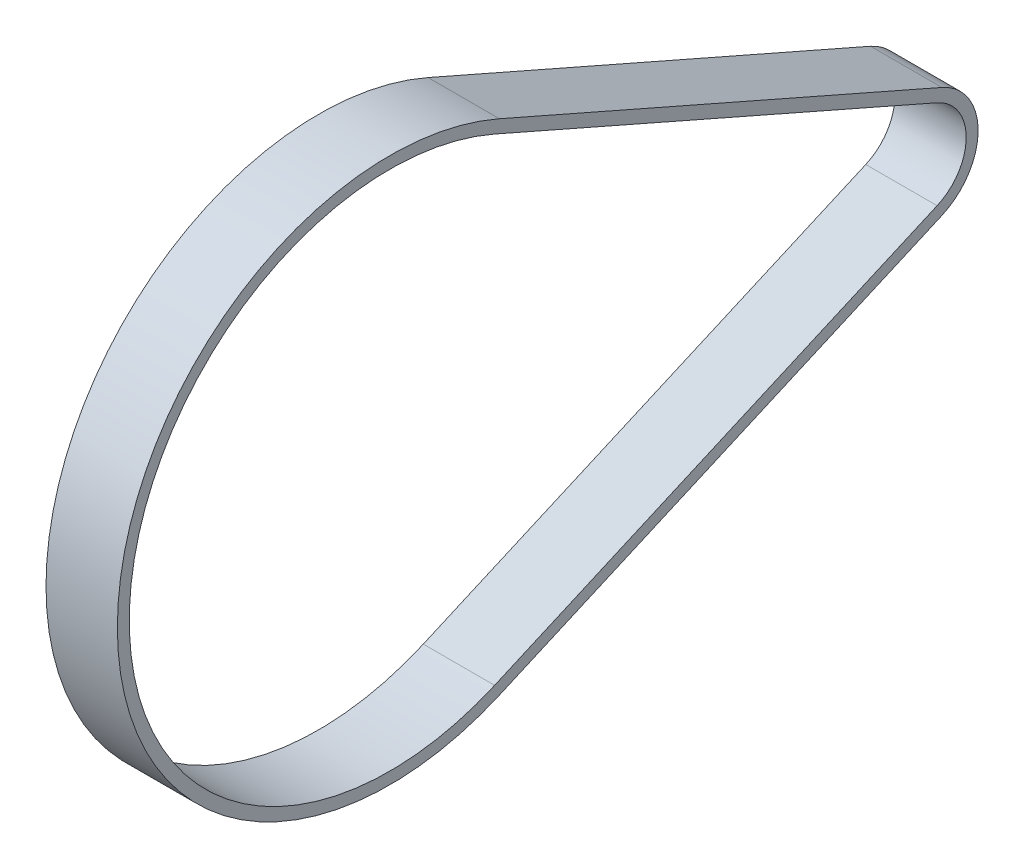
SolidWorks part; units mm, degrees
ref_plane "Front Plane" through (0, 0, 0) normal (0, 0, 1) x (1, 0, 0)
ref_plane "Top Plane" through (0, 0, 0) normal (0, 1, 0) x (1, 0, 0)
ref_plane "Right Plane" through (0, 0, 0) normal (1, 0, 0) x (0, 0, -1)
sketch "Sketch1" plane through (0, 0, 0) normal (1, 0, 0) x (0, 0, -1)
  line L0 (0, 37.672) -> (0, -29.9312) construction
  line L1 (-68.1193, 0) -> (49.7993, 0) construction
  line L2 (-32.4418, 52.4684) -> (60.5761, 11.6596)
  line L3 (-32.4418, -52.4684) -> (60.5761, -11.6596)
  line L4 (-55.4607, 57.2958) -> (-55.4607, 0) construction
  line L5 (-55.4607, 0) -> (-60.4544, 57.0778) construction
  line L6 (55.4607, 0) -> (67.2239, 4.8725) construction
  line L9 (-33.4462, 50.1791) -> (59.5717, 9.3703)
  line L10 (-33.4462, -50.1791) -> (59.5717, -9.3703)
  arc A0 (-32.4418, 52.4684) -> (-32.4418, -52.4684) centre (-55.4607, 0) ccw
  arc A1 (60.5761, -11.6596) -> (60.5761, 11.6596) centre (55.4607, 0) ccw
  arc A4 (59.5717, -9.3703) -> (59.5717, 9.3703) centre (55.4607, 0) ccw
  arc A5 (-33.4462, 50.1791) -> (-33.4462, -50.1791) centre (-55.4607, 0) ccw
  point P6 (85.003, 0)
  point P14 (-66.2011, 111.3818)
  dimension "D4" = 57.2958
  dimension "D5" = 12.7324
  dimension "D1" = 5
  dimension "D2" = 22.5
  dimension "D6" = 110.9215
  dimension "D7" = 2.5
extrude "Boss-Extrude1" add sketch "Sketch1" along normal mid plane 15
equation "\"D1@Sketch1\"=360/\"LARGE_TEETH\""
equation "\"D2@Sketch1\"=360/\"SMALL_TEETH\""
equation "\"LARGE_TEETH\"= 72"
equation "\"SMALL_TEETH\"= 16"
equation "\"BELT_LENGTH\"= 460mm"
equation "\"PITCH\"= 5mm"
equation "\"LARGE_C\"= \"LARGE_TEETH\" * \"PITCH\""
equation "\"SMALL_C\"= \"SMALL_TEETH\" * \"PITCH\""
equation "\"LARGE_RADIUS\"= \"LARGE_C\" / ( 2 * PI )"
equation "\"SMALL_RADIUS\"= \"SMALL_C\" / ( 2 * PI )"
equation "\"D4@Sketch1\"=\"LARGE_RADIUS\""
equation "\"D5@Sketch1\"=\"SMALL_RADIUS\""
equation "\"D3@Sketch1\"=\"BELT_LENGTH\""
